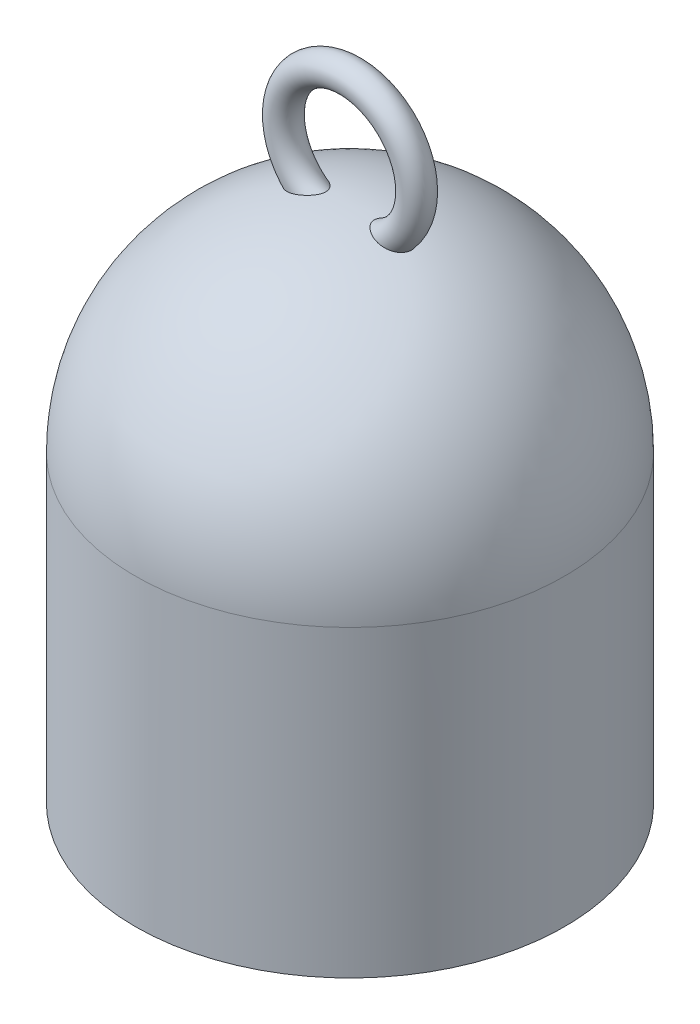
SolidWorks part; units mm, degrees
ref_plane "Front Plane" through (0, 0, 0) normal (0, 0, 1) x (1, 0, 0)
ref_plane "Top Plane" through (0, 0, 0) normal (0, 1, 0) x (1, 0, 0)
ref_plane "Right Plane" through (0, 0, 0) normal (1, 0, 0) x (0, 0, -1)
sketch "Sketch1" plane through (0, 0, 0) normal (0, 0, 1) x (1, 0, 0)
  line L0 (0, 0) -> (0, 88.9)
  line L1 (0, 0) -> (-36.83, 0)
  line L2 (-36.83, 0) -> (-36.83, 52.07)
  line L3 (-36.83, 52.07) -> (0, 52.07) construction
  arc A0 (0, 88.9) -> (-36.83, 52.07) centre (0, 52.07) ccw
  dimension "D3" = 52.07
  dimension "D1" = 88.9
  dimension "D2" = 36.83
revolve "Dome" add sketch "Sketch1" angle 360 about L0
sketch "Sketch2" plane through (0, 0, 0) normal (1, 0, 0) x (0, 0, -1)
  line L0 (0, 0) -> (0, 107.0912) construction
  line L1 (-12.6718, 96.52) -> (12.6718, 96.52) construction
  circle A0 centre (0, 85.09) radius 2.54
  arc A1 (36.83, 52.07) -> (-36.83, 52.07) centre (0, 52.07) ccw construction
  point P10 (0, 96.52)
  dimension "D1" = 5.08
  dimension "D2" = 33.02
  dimension "D3" = 11.43
revolve "Revolve1" add sketch "Sketch2" angle 360 about L1
shell "Shell1" thickness 1.27 removed face at (0, 0, -36.83)
thread "Thread1" pitch 2 method extrude profile "Thread Profile1" start angle 0, offset 0, length 10, pitch 2, diameter 71.12
ref_plane "Plane1" through (35.56, 0, 0) normal (0, 0, 1) x (1, 0, 0)
sketch "Thread Profile1" plane through (35.56, 0, 0) normal (0, 0, 1) x (1, 0, 0)
  line L0 (0, 0) -> (0, 2) construction
  line L11 (0, 0) -> (0, 1.75)
  line L12 (0, 1.75) -> (-1.0825, 1.125)
  line L13 (-1.0825, 1.125) -> (-1.0825, 0.625)
  line L15 (-1.0825, 0.625) -> (0, 0)
  line L17 (-1.0825, 0.875) -> (0, 0.875) construction
  point P2 (0, 0)
  dimension "Pitch" = 2
  dimension "Profile_Angle" = 60
  dimension "Profile_Land" = 0.5
  dimension "Profile_Height" = 1.0825
